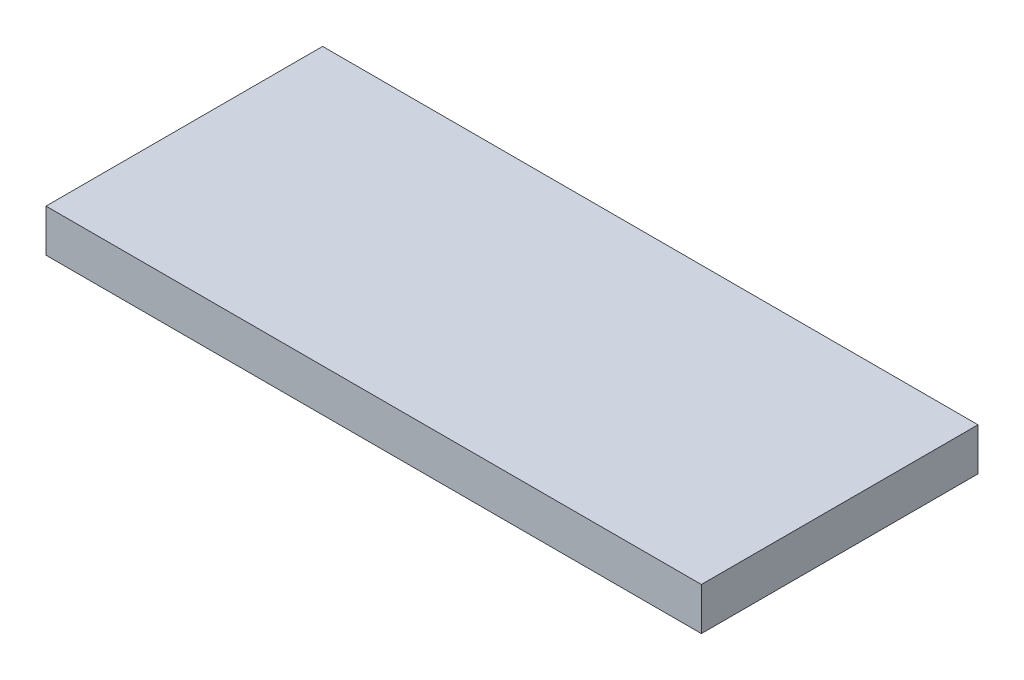
SolidWorks part; units mm, degrees
ref_plane "Front Plane" through (0, 0, 0) normal (0, 0, 1) x (1, 0, 0)
ref_plane "Top Plane" through (0, 0, 0) normal (0, 1, 0) x (1, 0, 0)
ref_plane "Right Plane" through (0, 0, 0) normal (1, 0, 0) x (0, 0, -1)
sketch "Sketch1" plane through (0, 0, 0) normal (0, 1, 0) x (1, 0, 0)
  line L1 (77, 32.5) -> (-77, 32.5)
  line L2 (77, 32.5) -> (77, -32.5)
  line L3 (77, -32.5) -> (-77, -32.5)
  line L4 (-77, 32.5) -> (-77, -32.5)
  line L5 (77, 32.5) -> (-77, -32.5) construction
  line L6 (77, -32.5) -> (-77, 32.5) construction
  point P0 (0, 0)
  dimension "D1" = 154
  dimension "D2" = 65
extrude "base" add sketch "Sketch1" along normal blind 10 contours L1 L4 L3 L2
sketch "Sketch2" plane through (0, 0, 0) normal (0, -1, 0) x (1, 0, 0)
  circle A0 centre (0, 0) radius 3
  dimension "D1" = 6
extrude "load cell button cut" [suppressed] cut sketch "Sketch2" against normal blind 2
sketch "Sketch4" plane through (0, 0, 0) normal (1, 0, 0) x (0, 0, -1)
  line L0 (3, 0) -> (3, 2)
  line L1 (3, 2) -> (0, 3.7321)
  line L2 (0, 3.7321) -> (0, 0) construction
  line L3 (0, 0) -> (3, 0)
  line L4 (0, 3.7321) -> (0, 0)
  dimension "D1" = 3
  dimension "D2" = 2
  dimension "D3" = 60
revolve "Cut-Revolve1" [suppressed] cut sketch "Sketch4" angle 360 about L2
equation "\"D2@Sketch1\"=65"
equation "\"D1@Sketch1\"=144+10"
